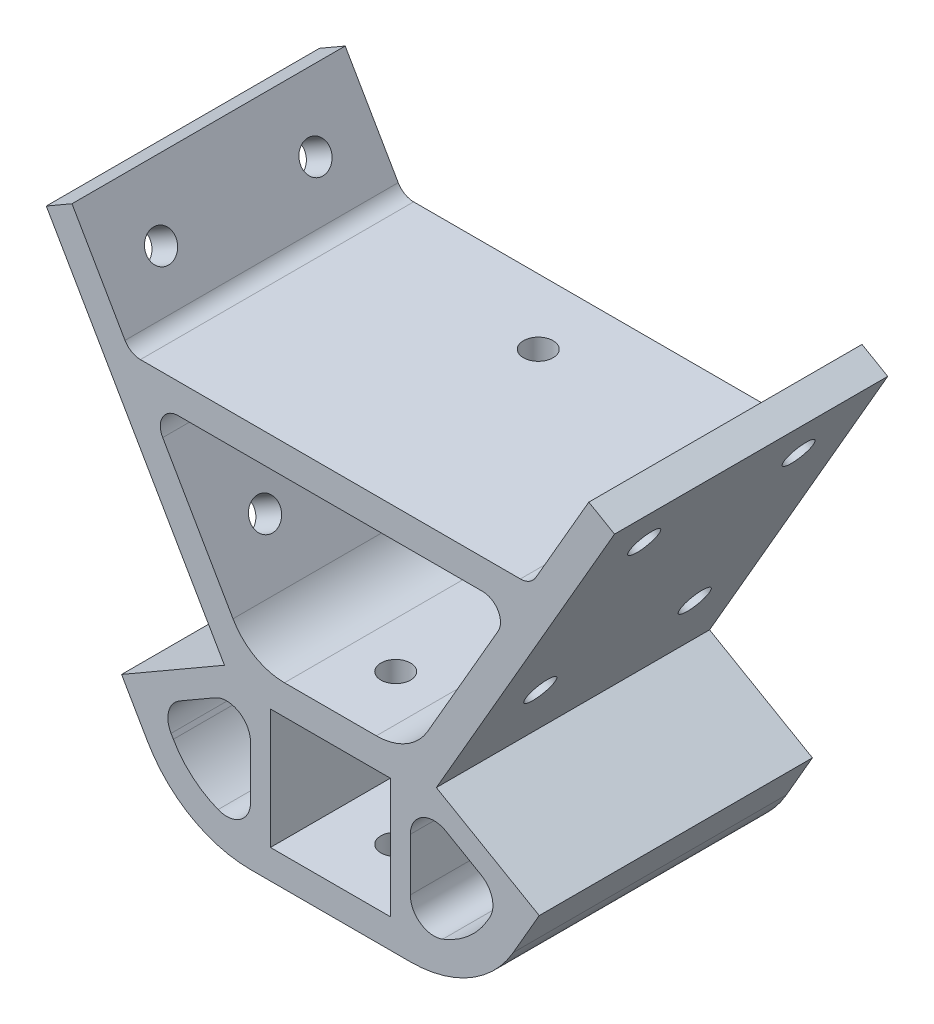
SolidWorks part; units mm, degrees
material "ABS generico"
ref_plane "Piano frontale" through (0, 0, 0) normal (0, 0, 1) x (1, 0, 0)
ref_plane "Piano superiore" through (0, 0, 0) normal (0, 1, 0) x (1, 0, 0)
ref_plane "Piano destro" through (0, 0, 0) normal (1, 0, 0) x (0, 0, -1)
sketch "Schizzo1" plane through (0, 0, 0) normal (0, 0, 1) x (1, 0, 0)
  line L0 (25, 0) -> (-25, 0)
  line L1 (-25, 0) -> (-35.1614, 17.6)
  line L2 (-35.1614, 17.6) -> (-17.8409, 27.6)
  line L3 (-17.8409, 27.6) -> (-47.8409, 79.5615)
  line L4 (-47.8409, 79.5615) -> (-43.5107, 82.0615)
  line L5 (-10.1, 25.1) -> (10.1, 25.1)
  line L6 (-10.1, 25.1) -> (-10.1, 4.9)
  line L7 (-10.1, 4.9) -> (10.1, 4.9)
  line L8 (10.1, 25.1) -> (10.1, 4.9)
  line L9 (-10.1, 25.1) -> (10.1, 4.9) construction
  line L10 (-10.1, 4.9) -> (10.1, 25.1) construction
  line L11 (-43.5107, 82.0615) -> (-13.5107, 30.1)
  line L12 (-13.5107, 30.1) -> (13.5107, 30.1)
  line L13 (-17.8409, 27.6) -> (-13.5107, 30.1) construction
  line L14 (0, 30.1) -> (0, 0) construction
  line L15 (25, 0) -> (35.1614, 17.6)
  line L16 (35.1614, 17.6) -> (17.8409, 27.6)
  line L17 (43.5107, 82.0615) -> (13.5107, 30.1)
  line L18 (47.8409, 79.5615) -> (43.5107, 82.0615)
  line L19 (17.8409, 27.6) -> (47.8409, 79.5615)
  point P11 (0, 15)
  point P19 (0, 0)
  dimension "D6" = 5
  dimension "D1" = 25
  dimension "D2" = 120
  dimension "D3" = 5
  dimension "D4" = 60
  dimension "D5" = 20
  dimension "D7" = 20.2
  dimension "D8" = 20.2
  dimension "D9" = 15
extrude "Estrusione-Estrusione1" add sketch "Schizzo1" along normal blind 46
fillet "Raccordo1" radius 20 2 edges at (25, 0, 23) (-25, 0, 23)
sketch "Schizzo8" plane through (-1.4295, -0.8253, 0) normal (-0.866, -0.5, 0) x (0, 0, 1)
  line L0 (10, 92.8227) -> (10, 32.8227) construction
  line L1 (46, 92.8227) -> (0, 92.8227) construction
  line L2 (46, 32.8227) -> (0, 32.8227) construction
  line L3 (23, 92.8227) -> (23, 32.8227) construction
  line L5 (0, 92.8227) -> (0, 32.8227) construction
  line L6 (46, 32.8227) -> (0, 32.8227) construction
  line L7 (36, 92.8227) -> (36, 32.8227) construction
  circle A0 centre (10, 82.8227) radius 2.5
  circle A1 centre (10, 47.8227) radius 2.5
  circle A2 centre (36, 47.8227) radius 2.5
  circle A3 centre (36, 82.8227) radius 2.5
  dimension "D2" = 10
  dimension "D6" = 5
  dimension "D1" = 10
  dimension "D3" = 15
extrude "Taglio-Estrusione3" cut sketch "Schizzo8" against normal blind 5
mirror "Specchia1" about plane through (0, 0, 0) normal (1, 0, 0) of "Taglio-Estrusione3"
sketch "Schizzo10" plane through (0, 0, 0) normal (0, 0, -1) x (-1, 0, 0)
  line L1 (-28.8312, 16.6359) -> (-13.453, 25.5145)
  line L2 (-26.4434, 12.5) -> (-30.8312, 20.1)
  line L3 (-26.4434, 12.5) -> (-28.8312, 16.6359)
  line L4 (0, 30.1) -> (0, 0) construction
  line L5 (-13.453, 25.5145) -> (-13.453, 5)
  line L6 (-10.1, 4.9) -> (-10.1, 25.1) construction
  line L7 (-35.1614, 17.6) -> (-17.8409, 27.6) construction
  line L8 (-13.5107, 30.1) -> (13.5107, 30.1) construction
  line L9 (13.453, 25.5145) -> (13.453, 5)
  line L10 (26.4434, 12.5) -> (28.8312, 16.6359)
  line L11 (28.8312, 16.6359) -> (13.453, 25.5145)
  arc A1 (26.4434, 12.5) -> (13.453, 5) centre (13.453, 20) cw
  arc A2 (-26.4434, 12.5) -> (-13.453, 5) centre (-13.453, 20) ccw
  arc A3 (-26.4434, 12.5) -> (-13.453, 5) centre (-13.453, 20) ccw
  dimension "D2" = 4
  dimension "D1" = 5
extrude "Taglio-Estrusione4" cut sketch "Schizzo10" against normal through all
fillet "Raccordo2" radius 10 2 edges at (13.5107, 30.1, 23) (-13.5107, 30.1, 23)
fillet "Raccordo3" radius 4 6 edges at (-13.453, 5, 23) (-28.8312, 16.6359, 23) (28.8312, 16.6359, 23) (13.453, 5, 23) (13.453, 25.5145, 23) (-13.453, 25.5145, 23)
sketch "Schizzo11" plane through (0, 0, 0) normal (0, -1, 0) x (1, 0, 0)
  line L0 (0, 46) -> (0, 0) construction
  line L1 (-13.453, 46) -> (13.453, 46) construction
  circle A0 centre (0, 35) radius 2.5
  circle A1 centre (0, 11) radius 2.5
  point P9 (0, 23)
  dimension "D1" = 5
  dimension "D2" = 24
  dimension "D3" = 12
extrude "Taglio-Estrusione5" cut sketch "Schizzo11" against normal through all
sketch "Schizzo13" plane through (0, 0, 0) normal (0, 0, -1) x (-1, 0, 0)
  line L0 (-33.718, 65.1) -> (33.718, 65.1)
  line L1 (-43.5107, 82.0615) -> (-16.3975, 35.1) construction
  line L2 (16.3975, 35.1) -> (43.5107, 82.0615) construction
  line L3 (33.718, 65.1) -> (30.8312, 60.1)
  line L4 (30.8312, 60.1) -> (-30.8312, 60.1)
  line L5 (-30.8312, 60.1) -> (-33.718, 65.1)
  line L6 (-7.7372, 30.1) -> (7.7372, 30.1) construction
  dimension "D1" = 5
  dimension "D2" = 30
extrude "Estrusione-Estrusione2" add sketch "Schizzo13" along direction (0, 0, -1) on the side against the normal up to surface (46 mm away) up to face at (-20.5154, 14.3826, 46)
fillet "Raccordo4" radius 3 4 edges at (-30.8312, 60.1, 23) (30.8312, 60.1, 23) (-33.718, 65.1, 23) (33.718, 65.1, 23)
extrude "Taglio-Estrusione6" cut sketch "Schizzo11<3>" against normal through all contours A1
sketch "Schizzo11<3>" plane through (0, 0, 0) normal (0, -1, 0) x (1, 0, 0) same geometry as "Schizzo11"
